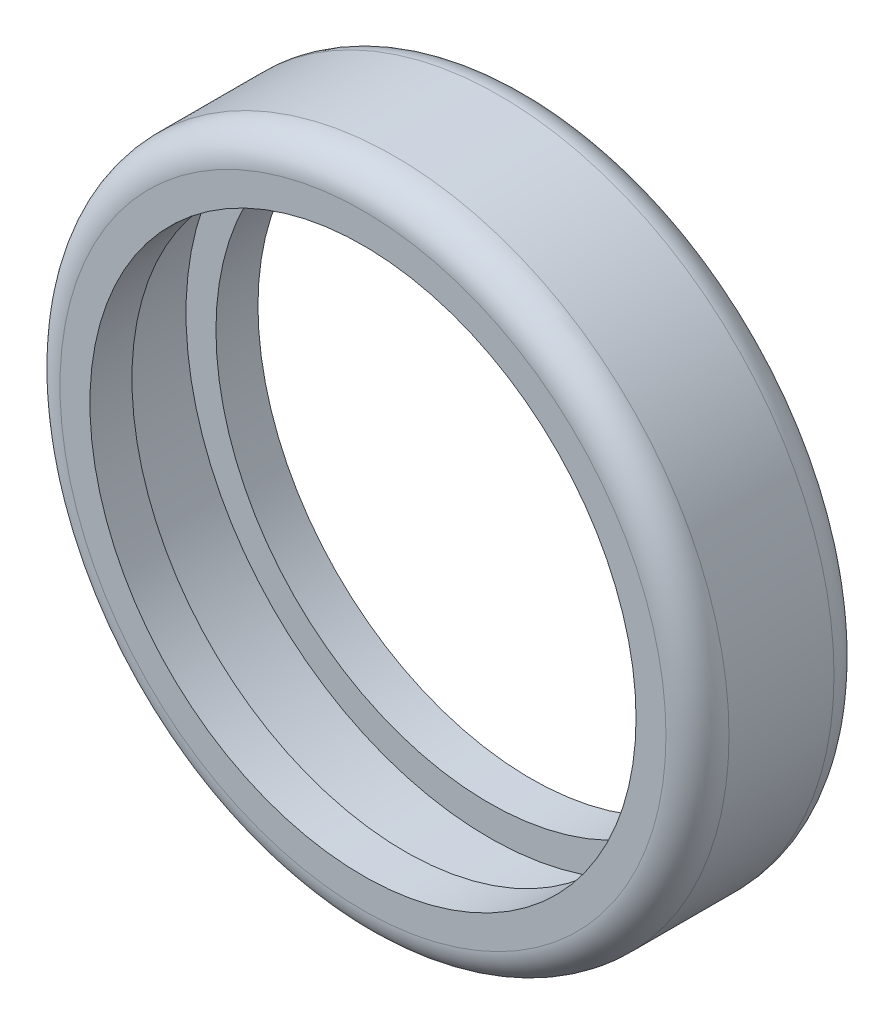
SolidWorks part; units mm, degrees
ref_plane "Plan de face" through (0, 0, 0) normal (0, 0, 1) x (1, 0, 0)
ref_plane "Plan de dessus" through (0, 0, 0) normal (0, 1, 0) x (1, 0, 0)
ref_plane "Plan de droite" through (0, 0, 0) normal (1, 0, 0) x (0, 0, -1)
sketch "Esquisse1" plane through (0, 0, 0) normal (0, 0, 1) x (1, 0, 0)
  circle A0 centre (0, 0) radius 28.85
  circle A1 centre (0, 0) radius 31.85
extrude "Boss.-Extru.1" add sketch "Esquisse1" along normal blind 8 contours A1 A0
sketch "Esquisse2" plane through (0, 0, 8) normal (0, 0, 1) x (1, 0, 0)
  circle A0 centre (0, 0) radius 26
  circle A1 centre (0, 0) radius 31.85
extrude "Boss.-Extru.2" add sketch "Esquisse2" along normal blind 4
sketch "Esquisse3" plane through (0, 0, 0) normal (0, 0, -1) x (-1, 0, 0)
  circle A0 centre (0, 0) radius 31.85
  circle A3 centre (0, 0) radius 26
extrude "Boss.-Extru.3" add sketch "Esquisse3" along normal blind 4
fillet "Congé1" radius 3 2 edges at (31.85, 0, 12) (-31.85, 0, -4)
